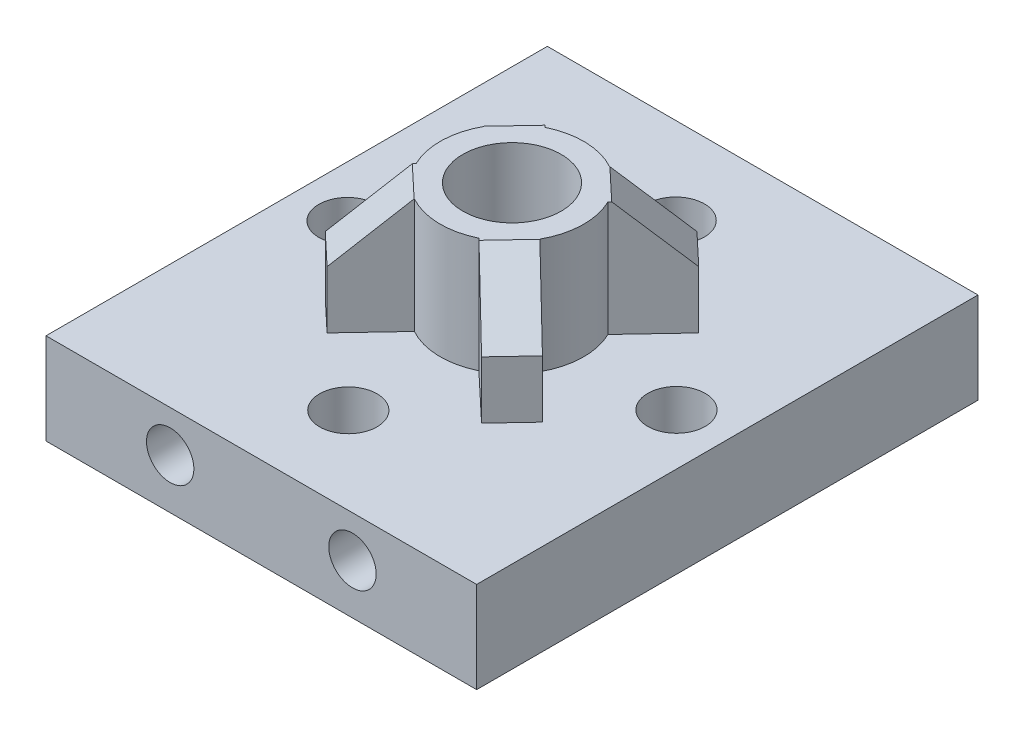
SolidWorks part; units mm, degrees
ref_plane "Front Plane" through (0, 0, 0) normal (0, 0, 1) x (1, 0, 0)
ref_plane "Top Plane" through (0, 0, 0) normal (0, 1, 0) x (1, 0, 0)
ref_plane "Right Plane" through (0, 0, 0) normal (1, 0, 0) x (0, 0, -1)
sketch "Sketch1" plane through (0, 0, 0) normal (0, 0, 1) x (1, 0, 0)
  line L1 (0, 0) -> (30, 0)
  line L2 (0, 0) -> (0, 6.35)
  line L3 (0, 6.35) -> (30, 6.35)
  line L4 (30, 0) -> (30, 6.35)
  dimension "D1" = 30
  dimension "D2" = 6.35
extrude "Boss-Extrude1" add sketch "Sketch1" along normal blind 34.925
sketch "Sketch2" plane through (0, 0, 34.925) normal (0, 0, 1) x (1, 0, 0)
  line L0 (0, 6.35) -> (0, 0) construction
  line L1 (30, 6.35) -> (0, 6.35) construction
  circle A0 centre (8.65, 3.4721) radius 1.651
  circle A1 centre (21.35, 3.4721) radius 1.651
  point P5 (0, 3.175)
  point P6 (15, 6.35)
  dimension "D1" = 3.302
  dimension "D2" = 12.7
  dimension "D3" = 6.35
extrude "Cut-Extrude1" cut sketch "Sketch2" against normal blind 15
ref_plane "Plane1" through (0, 0, 17.4625) normal (0, 0, 1) x (1, 0, 0)
mirror "Mirror1" about plane through (0, 0, 17.4625) normal (0, 0, 1) of "Cut-Extrude1"
sketch "Sketch3" plane through (0, 6.35, 0) normal (0, 1, 0) x (1, 0, 0)
  line L0 (30, 0) -> (0, 0) construction
  line L1 (0, -34.925) -> (0, 0) construction
  circle A0 centre (15, -17.4625) radius 3.429
  point P2 (15, 0)
  point P3 (0, -17.4625)
  dimension "D1" = 6.858
extrude "Cut-Extrude2" cut sketch "Sketch3" against normal through all
sketch "Sketch4" plane through (0, 6.35, 0) normal (0, 1, 0) x (1, 0, 0)
  circle A0 centre (15, -17.4625) radius 3.429
  circle A1 centre (15, -17.4625) radius 5
  circle A2 centre (15, -17.4625) radius 3.429 construction
  dimension "D1" = 10
extrude "Boss-Extrude2" add sketch "Sketch4" along normal blind 8
sketch "Sketch5" plane through (0, 6.35, 0) normal (0, 1, 0) x (1, 0, 0)
  line L0 (15, -17.4625) -> (5.5218, -7.9843) construction
  line L5 (15, -17.4625) -> (4.7235, -17.4625) construction
  line L6 (7.4984, -12.0813) -> (11.1369, -15.5107)
  line L7 (7.4984, -12.0813) -> (9.556, -9.8981)
  line L8 (11.1369, -15.5107) -> (13.1946, -13.3276)
  line L9 (9.556, -9.8981) -> (13.1946, -13.3276)
  point P0 (8.5272, -10.9897)
  point P3 (0, 0)
  point P4 (15, -17.4625)
  dimension "D1" = 3
  dimension "D2" = 5
  dimension "D3" = 45
extrude "Boss-Extrude3" add sketch "Sketch5" along normal up to surface (8 mm away) up to face at (15, 14.35, 22.4625)
sketch "Sketch6" plane through (0, 6.35, 0) normal (0, 1, 0) x (1, 0, 0)
  circle A0 centre (14.9729, -6.0325) radius 2
  circle A1 centre (15, -17.4625) radius 3.429 construction
  dimension "D2" = 4
  dimension "D1" = 11.43
extrude "Cut-Extrude3" cut sketch "Sketch6" against normal through all
pattern_circular "CirPattern2" count 4 over 360 about axis through (15, 0, 17.4625) along (0, 1, 0) of "Cut-Extrude3"
chamfer "Chamfer1" distance 4 angle 47 1 edges at (8.5272, 14.35, 10.9897) first distance on face at (8.5272, 10.35, 10.9897)
pattern_circular "CirPattern3" count 4 over 360 about axis through (15, 14.35, 17.4625) along (0, -1, 0) of "Boss-Extrude3", "Chamfer1"
